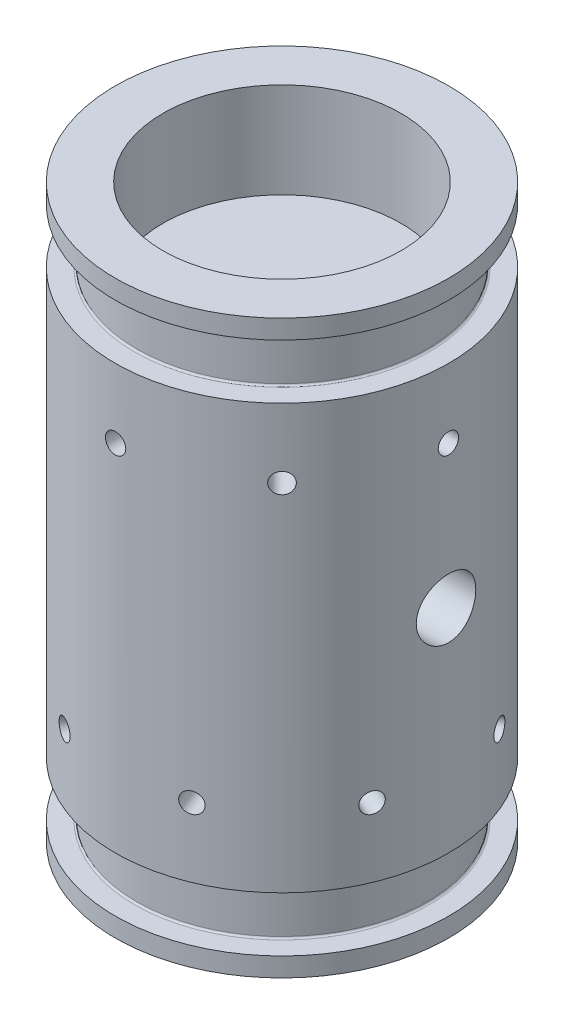
SolidWorks part; units mm, degrees
material "6063-T6"
ref_plane "Front Plane" through (0, 0, 0) normal (0, 0, 1) x (1, 0, 0)
ref_plane "Top Plane" through (0, 0, 0) normal (0, 1, 0) x (1, 0, 0)
ref_plane "Right Plane" through (0, 0, 0) normal (1, 0, 0) x (0, 0, -1)
sketch "Sketch1" plane through (0, 0, 0) normal (0, 1, 0) x (1, 0, 0)
  circle A0 centre (0, 0) radius 22.225
  dimension "D1" = 44.45
extrude "body" add sketch "Sketch1" along normal mid plane 76.2
sketch "Sketch2" plane through (0, 38.1, 0) normal (0, 1, 0) x (1, 0, 0)
  circle A0 centre (0, 0) radius 15.875
  dimension "D1" = 31.75
extrude "\"lightening hole\"" cut sketch "Sketch2" against normal blind 12.7
sketch "main-o-ring" plane through (0, 0, 0) normal (0, 0, 1) x (1, 0, 0)
  line L0 (0, 0) -> (0, 33.5592) construction
  line L1 (-22.225, 35.56) -> (-22.225, 28.2702)
  line L2 (-22.225, 35.56) -> (-19.6204, 35.56)
  line L3 (-19.3802, 35.3198) -> (-19.3802, 28.5104)
  line L4 (-19.6204, 28.2702) -> (-22.225, 28.2702)
  line L5 (22.225, 38.1) -> (-22.225, 38.1) construction
  arc A0 (-19.3802, 28.5104) -> (-19.6204, 28.2702) centre (-19.6204, 28.5104) cw
  arc A1 (-19.6204, 35.56) -> (-19.3802, 35.3198) centre (-19.6204, 35.3198) cw
  dimension "D5" = 0.2402
  dimension "D1" = 44.45
  dimension "D2" = 7.2898
  dimension "D3" = 2.54
  dimension "D4" = 2.8448
revolve "o-ring-main (with backup rings)" cut sketch "main-o-ring" angle 360 about L0
mirror "Top-Bottom Symmetry" about plane through (0, 0, 0) normal (0, 1, 0) of "o-ring-main (with backup rings)", "\"lightening hole\""
hole_wizard "#6-32 Tapped Hole1" positions "3DSketch1" profile "Sketch3" tap size "#6-32" standard "ANSI Inch"
sketch3d "3DSketch1"
  point P0 (-22.225, 19.05, 0)
  dimension "D1" = 19.05
sketch "Sketch3" plane through (-22.225, 19.05, 0) normal (0, 1, 0) x (0, 0, 1)
  line L0 (0, 0) -> (0, 8.7629)
  line L1 (0, 8.7629) -> (1.3525, 7.9502)
  line L2 (1.3525, 7.9502) -> (1.3525, 0)
  line L5 (1.3525, 0) -> (0, 0)
  line L10 (0, 8.7629) -> (-1.3526, 7.9502) construction
  line L11 (0, -6.35) -> (0, 107.95) construction
  dimension "Tap Drill Dia." = 2.7051
  dimension "Tap Drill Depth" = 7.9502
  dimension "Drill Angle" = 118
cosmetic thread "Hole Thread1" parameters "D1"=7.0104, "D2"=3.5052
ref_plane "Offset Reference" through (-20.5332, 0, -8.5051) normal (-0.9239, 0, -0.3827) x (0, -1, 0)
hole_wizard "#6-32 Tapped Hole2" positions "3DSketch2" profile "Sketch4" tap size "#6-32" standard "ANSI Inch"
sketch3d "3DSketch2"
  point P0 (-20.5332, -19.05, -8.5051)
  dimension "D1" = 19.05
sketch "Sketch4" plane through (-20.5332, -19.05, -8.5051) normal (0, 1, 0) x (-0.3827, 0, 0.9239)
  line L0 (0, 0) -> (0, 8.7629)
  line L1 (0, 8.7629) -> (1.3525, 7.9502)
  line L2 (1.3525, 7.9502) -> (1.3525, 0)
  line L5 (1.3525, 0) -> (0, 0)
  line L10 (0, 8.7629) -> (-1.3526, 7.9502) construction
  line L11 (0, -6.35) -> (0, 107.95) construction
  dimension "Tap Drill Dia." = 2.7051
  dimension "Tap Drill Depth" = 7.9502
  dimension "Drill Angle" = 118
cosmetic thread "Hole Thread9" parameters "D1"=7.0104, "D2"=3.5052
pattern_circular "Tapped Hole Pattern" count 8 over 360 about axis through (0, 38.1, 0) along (0, -1, 0) of "#6-32 Tapped Hole1", "#6-32 Tapped Hole2"
cosmetic thread "Hole Thread2" parameters "D1"=7.0104, "D2"=3.5052
cosmetic thread "Hole Thread3" parameters "D1"=7.0104, "D2"=3.5052
cosmetic thread "Hole Thread4" parameters "D1"=7.0104, "D2"=3.5052
cosmetic thread "Hole Thread5" parameters "D1"=7.0104, "D2"=3.5052
cosmetic thread "Hole Thread6" parameters "D1"=7.0104, "D2"=3.5052
cosmetic thread "Hole Thread7" parameters "D1"=7.0104, "D2"=3.5052
cosmetic thread "Hole Thread8" parameters "D1"=7.0104, "D2"=3.5052
cosmetic thread "Hole Thread10" parameters "D1"=7.0104, "D2"=3.5052
cosmetic thread "Hole Thread11" parameters "D1"=7.0104, "D2"=3.5052
cosmetic thread "Hole Thread12" parameters "D1"=7.0104, "D2"=3.5052
cosmetic thread "Hole Thread13" parameters "D1"=7.0104, "D2"=3.5052
cosmetic thread "Hole Thread14" parameters "D1"=7.0104, "D2"=3.5052
cosmetic thread "Hole Thread15" parameters "D1"=7.0104, "D2"=3.5052
cosmetic thread "Hole Thread16" parameters "D1"=7.0104, "D2"=3.5052
sketch "Sketch5" [suppressed] plane through (0, 25.4, 0) normal (0, 1, 0) x (1, 0, 0)
  circle A0 centre (0, 0) radius 22.225
  dimension "D1" = 44.45
extrude "top-reduce" [suppressed] cut sketch "Sketch5" against normal blind 12.7
sketch "Sketch6" [suppressed] plane through (0, -25.4, 0) normal (0, -1, 0) x (1, 0, 0)
  circle A0 centre (0, 0) radius 22.225
  dimension "D1" = 44.45
extrude "Cut-Extrude1" [suppressed] cut sketch "Sketch6" against normal blind 12.7
hole_wizard "1/4-20 (0.250) Piston Stop/Vent" positions "3DSketch3" profile "Sketch7" tap size "1/4-20" standard "ANSI Inch"
sketch3d "3DSketch3"
  point P0 (-22.225, 0, 0)
  point P3 (0, 0, 0)
sketch "Sketch7" plane through (-22.225, 0, 0) normal (0, 1, 0) x (0, 0, 1)
  line L0 (0, 0) -> (0, 9.1538)
  line L1 (0, 9.1538) -> (2.5527, 7.62)
  line L2 (2.5527, 7.62) -> (2.5527, 0)
  line L5 (2.5527, 0) -> (0, 0)
  line L10 (0, 9.1538) -> (-2.5527, 7.62) construction
  line L11 (0, -6.35) -> (0, 107.95) construction
  dimension "Tap Drill Dia." = 5.1054
  dimension "Tap Drill Depth" = 7.62
  dimension "Drill Angle" = 118
cosmetic thread "Hole Thread17" parameters "D1"=7.62, "D2"=6.35
hole_wizard "5/16 (0.3125) Piston Bore" positions "3DSketch4" profile "Sketch8" hole size "5/16" standard "ANSI Inch"
sketch3d "3DSketch4"
  point P0 (22.225, 0, 0)
  point P3 (0, 0, 0)
  point P4 (0, 0, 0)
  point P5 (0, 0, 0)
sketch "Sketch8" plane through (22.225, 0, 0) normal (0, 1, 0) x (0, 0, -1)
  line L0 (0, 0) -> (0, 38.4527)
  line L1 (0, 38.4527) -> (3.9687, 36.068)
  line L2 (3.9687, 36.068) -> (3.9687, 0)
  line L5 (3.9687, 0) -> (0, 0)
  line L10 (0, 38.4527) -> (-3.9688, 36.068) construction
  line L11 (0, -6.35) -> (0, 107.95) construction
  dimension "Hole Dia." = 7.9375
  dimension "Hole Depth" = 36.068
  dimension "Drill Angle" = 118
cosmetic thread "Hole Thread20" parameters "D1"=12.7, "D2"=9.525
hole_wizard "3/8-16 Thread Blast Cap" positions "3DSketch6" profile "Sketch11" tap size "3/8-16" standard "ANSI Inch"
sketch3d "3DSketch6"
  point P0 (22.225, 0, 0)
  point P3 (0, 0, 0)
  point P5 (22.225, 1.3319, -0.0086)
  point P7 (22.225, 0.0325, 0.017)
  point P9 (0, 0, 0)
  point P10 (0, 0, 0)
  point P11 (0, 0, 0)
  point P12 (0, 0, 0)
sketch "Sketch11" plane through (22.225, 0, 0) normal (0, 1, 0) x (0, 0, -1)
  line L0 (0, 0) -> (0, 11.9097)
  line L1 (0, 11.9097) -> (3.9687, 9.525)
  line L2 (3.9687, 9.525) -> (3.9687, 0)
  line L5 (3.9687, 0) -> (0, 0)
  line L10 (0, 11.9097) -> (-3.9688, 9.525) construction
  line L11 (0, -6.35) -> (0, 107.95) construction
  dimension "Tap Drill Dia." = 7.9375
  dimension "Tap Drill Depth" = 9.525
  dimension "Drill Angle" = 118
